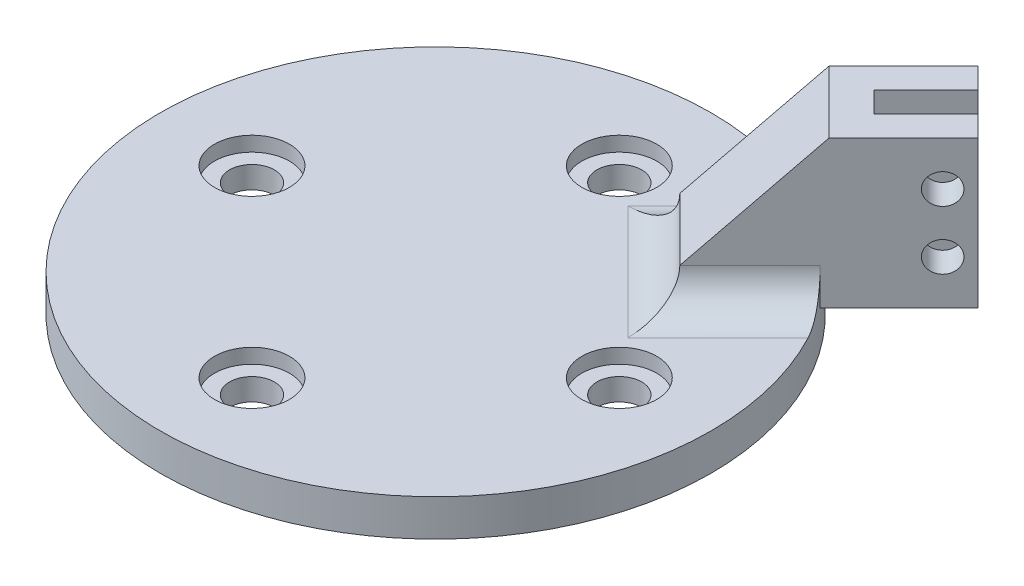
SolidWorks part; units mm, degrees
ref_plane "Front Plane" through (0, 0, 0) normal (0, 0, 1) x (1, 0, 0)
ref_plane "Top Plane" through (0, 0, 0) normal (0, 1, 0) x (1, 0, 0)
ref_plane "Right Plane" through (0, 0, 0) normal (1, 0, 0) x (0, 0, -1)
sketch "Sketch1" plane through (0, 0, 0) normal (0, 1, 0) x (1, 0, 0)
  line L0 (0, 37.5) -> (0, 0) construction
  line L5 (0, 0) -> (37.5, 0) construction
  circle A1 centre (0, 0) radius 37.5
  circle A2 centre (0, 25) radius 3.05
  circle A3 centre (0, 0) radius 25 construction
  circle A7 centre (25, 0) radius 3.05
  circle A8 centre (0, -25) radius 3.05
  circle A9 centre (-25, 0) radius 3.05
  point P17 (0, 0)
  point P18 (0, 0)
  dimension "D1" = 75
  dimension "D2" = 6.1
  dimension "D3" = 50
  dimension "D4" = 4
extrude "Boss-Extrude1" add sketch "Sketch1" along normal blind 5
sketch "Sketch2" plane through (0, 5, 0) normal (0, 1, 0) x (1, 0, 0)
  circle A0 centre (0, 25) radius 3.05 construction
  circle A1 centre (0, 25) radius 3.05
  circle A2 centre (0, 25) radius 5.1
  dimension "10.2" = 10.2
extrude "Cut-Extrude1" cut sketch "Sketch2" against normal blind 2
pattern_circular "CirPattern1" count 4 every 90 about axis through (0, 5, 0) along (0, 1, 0) of "Cut-Extrude1"
sketch "Sketch4" plane through (0, 5, 0) normal (0, 1, 0) x (1, 0, 0)
  line L0 (0, 0) -> (26.5165, 26.5165) construction
  line L5 (0, 0) -> (37.5, 0) construction
  line L6 (12.3744, 20.8597) -> (20.8597, 12.3744)
  line L7 (20.8597, 12.3744) -> (30.4175, 21.9323)
  line L8 (12.3744, 20.8597) -> (21.9323, 30.4175)
  line L10 (21.9323, 30.4175) -> (25.5973, 34.0825)
  line L11 (25.5973, 34.0825) -> (34.0825, 25.5973)
  line L12 (34.0825, 25.5973) -> (30.4175, 21.9323)
  circle A0 centre (0, 0) radius 37.5 construction
  arc A1 (37.5, 0) -> (30.4175, 21.9323) centre (0, 0) ccw
  point P12 (34.0794, 25.5941)
  circle M9 centre (0, 0) radius 37.5
  dimension "D4" = 4.7
  dimension "D1" = 45
  dimension "D2" = 12
  dimension "D3" = 14
extrude "Boss-Extrude2" add sketch "Sketch4" along normal blind 20 contours L8 L6 L7 M9 | L12 L11 L10 M9 region at (21.5105, 5, -21.5105) region at (28.1199, 5, -28.1199)
sketch "Sketch5" plane through (29.8399, 0, -29.8399) normal (0.7071, 0, -0.7071) x (-0.7071, 0, -0.7071)
  line L0 (37.5, 5) -> (-37.5, 5) construction
  line L1 (-6, 25) -> (-2, 25)
  line L2 (-6, 25) -> (-6, 5)
  line L3 (-6, 5) -> (-2, 5)
  line L4 (-2, 25) -> (-2, 5)
  line L5 (0, 25) -> (0, 0) construction
  line L6 (6, 25) -> (2, 25)
  line L7 (6, 25) -> (6, 5)
  line L8 (6, 5) -> (2, 5)
  line L9 (2, 25) -> (2, 5)
  point P14 (0, 0)
  point P15 (0, 0)
  point P17 (0, 0)
  point P18 (-3.5759, 23.2932)
  point P19 (4.0972, 22.5659)
  point P21 (0, 0)
  dimension "D1" = 4
extrude "Boss-Extrude3" add sketch "Sketch5" along normal blind 10
sketch "Sketch6" plane through (4.2426, 0, 4.2426) normal (0.7071, 0, 0.7071) x (0.7071, 0, -0.7071)
  line L0 (52.2, 25) -> (52.2, 5) construction
  line L1 (52.2, 15) -> (23.5, 15) construction
  line L2 (23.5, 25) -> (23.5, 5) construction
  circle A0 centre (48.8, 19) radius 2.05
  circle A1 centre (48.8, 11) radius 2.05
  point P4 (0, 0)
  point P11 (50.8, 11)
  dimension "D1" = 4.1
  dimension "D3" = 3.4
  dimension "D4" = 4.1
  dimension "D2" = 8
extrude "Cut-Extrude2" cut sketch "Sketch6" against normal blind 17
fillet "Fillet3" radius 5 3 edges at (17.1533, 5, -25.6386) (25.6386, 5, -17.1533) (16.617, 5, -16.617)
sketch "Sketch7" plane through (4.2426, 0, 4.2426) normal (0.7071, 0, 0.7071) x (0.7071, 0, -0.7071)
  line L0 (23.5, 10) -> (37.85, 25)
  line L1 (23.5, 25) -> (52.2, 25) construction
  line L2 (23.5, 10) -> (23.5, 25)
  line L3 (23.5, 25) -> (23.5, 10) construction
  line L4 (23.5, 25) -> (37.85, 25)
  point P6 (37.85, 25)
extrude "Cut-Extrude3" cut sketch "Sketch7" against normal blind 17
